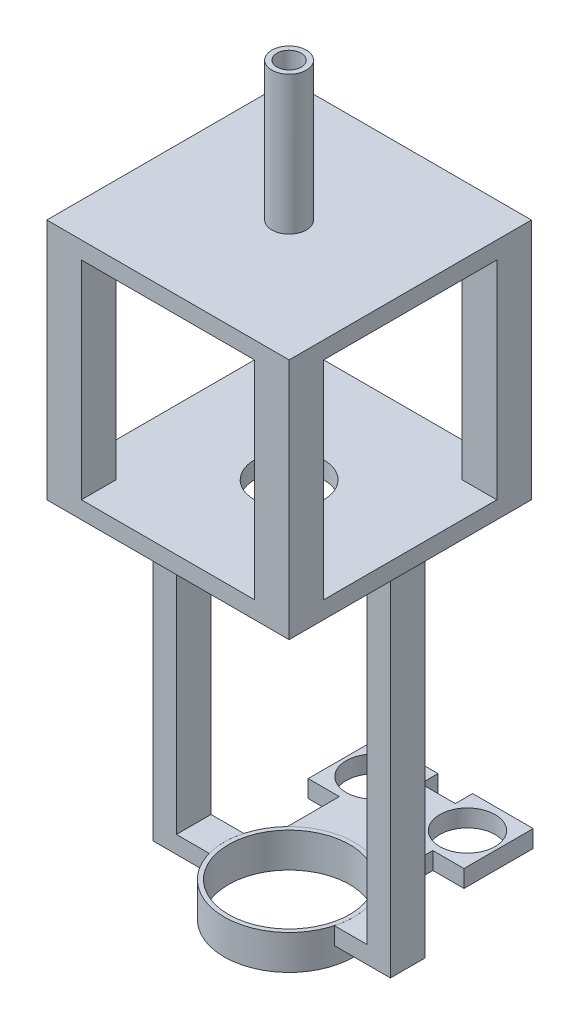
SolidWorks part; units mm, degrees
ref_plane "Front Plane" through (0, 0, 0) normal (0, 0, 1) x (1, 0, 0)
ref_plane "Top Plane" through (0, 0, 0) normal (0, 1, 0) x (1, 0, 0)
ref_plane "Right Plane" through (0, 0, 0) normal (1, 0, 0) x (0, 0, -1)
sketch "Sketch2" plane through (0, 0, 0) normal (0, 1, 0) x (1, 0, 0)
  line L0 (0, 17.5) -> (0, -17.5) construction
  line L1 (-17.5, 0) -> (17.5, 0) construction
  line L2 (-17.5, 0) -> (-17.5, 5) construction
  line L3 (-16.7705, 5) -> (-34.2705, 5)
  line L4 (-34.2705, 5) -> (-34.2705, -5)
  line L5 (-16.7705, -5) -> (-34.2705, -5)
  line L6 (16.7705, -5) -> (34.2705, -5)
  line L7 (34.2705, 5) -> (34.2705, -5)
  line L8 (16.7705, 5) -> (34.2705, 5)
  line L9 (0, 28.012) -> (22.5, 28.012)
  line L10 (22.5, 28.012) -> (22.5, 48.012)
  line L11 (22.5, 48.012) -> (5, 48.012)
  line L12 (-22.5, 48.012) -> (-22.5, 28.012)
  line L13 (-22.5, 28.012) -> (0, 28.012)
  line L14 (22.5, 38.012) -> (21.5, 38.012) construction
  line L20 (-5, 48.012) -> (-22.5, 48.012)
  line L21 (0, 43.012) -> (0, 28.012) construction
  line L22 (-5, 48.012) -> (-5, 43.012)
  line L23 (-5, 43.012) -> (5, 43.012)
  line L24 (5, 43.012) -> (5, 48.012)
  line L25 (13.5, 46.012) -> (13.5, 48.012) construction
  line L26 (13.5, 30.012) -> (13.5, 28.012) construction
  line L27 (-13.5, 38.012) -> (13.5, 38.012) construction
  line L28 (-13.5, 13.012) -> (-13.5, 28.012)
  line L29 (13.5, 28.012) -> (13.5, 13.012)
  line L30 (-18.75, 0) -> (-27.55, 0) construction
  line L31 (-27.55, 5) -> (-27.55, -5)
  line L32 (27.55, 5) -> (27.55, -5)
  circle A0 centre (0, 0) radius 17.5
  circle A1 centre (0, 0) radius 18.75
  circle A2 centre (13.5, 38.012) radius 8
  circle A3 centre (-13.5, 38.012) radius 8
  point P13 (-34.2705, 0)
  dimension "D1" = 35
  dimension "D2" = 17.5
  dimension "D4" = 37.5
  dimension "D8" = 1
  dimension "D9" = 16
  dimension "D3" = 5
  dimension "D5" = 5
  dimension "D6" = 20
  dimension "D7" = 45
  dimension "D10" = 17.5
  dimension "D11" = 8.8
  dimension "D12" = 27
  dimension "D13" = 15
extrude "Connector sleeve" add sketch "Sketch2" along normal blind 5 and the other way blind 5 contours L5 A1 L6 A0 | L8 A1 L3 A0 | L6 A1 L8 A0 | L3 A1 L5 A0 region at (-15.95, 0, -9.0999) region at (-17.8897, 0, 0) region at (-17.4208, 0, 5.3867) region at (17.8897, 0, 0)
ref_plane "Plane2" through (0, 30, 0) normal (0, 1, 0) x (1, 0, 0)
extrude "Sensor holder" add sketch "Sketch2<10>" along normal blind 5 separate body contours L24 L23 L22 L20 L12 L13 L9 L10 L11 A2 A3 | A1 L29 L9 L13 L28 | A1 L3 L31 L5 | L31 L3 L4 L5 | A1 L6 L32 L8 | L8 L32 L6 L7 region at (-30.9103, 0, 0) region at (-23.0354, 0, 0) region at (0, 0, -22.3672) region at (0, 0, -37.1747) region at (23.0354, 0, 0) region at (30.9103, 0, 0)
sketch "Sketch2<10>" plane through (0, 0, 0) normal (0, 1, 0) x (1, 0, 0) same geometry as "Sketch2"
extrude "Boss-Extrude1" add sketch "Sketch2<18>" along normal blind 100 contours L31 L3 L4 L5 | L8 L32 L6 L7 region at (-30.9103, 0, 0) region at (30.9103, 0, 0)
sketch "Sketch2<18>" plane through (0, 0, 0) normal (0, 1, 0) x (1, 0, 0) same geometry as "Sketch2"
sketch "Sketch4" plane through (0, 100, 0) normal (0, 1, 0) x (1, 0, 0)
  line L1 (-35, -35) -> (35, -35)
  line L2 (-35, -35) -> (-35, 35)
  line L3 (-35, 35) -> (35, 35)
  line L4 (35, -35) -> (35, 35)
  line L5 (-35, -35) -> (35, 35) construction
  line L6 (-35, 35) -> (35, -35) construction
  circle A0 centre (0, 0) radius 10
  point P0 (0, 0)
  dimension "D2" = 20
  dimension "D1" = 70
extrude "Boss-Extrude2" add sketch "Sketch4" along normal blind 5
sketch "Sketch6" plane through (0, 105, 0) normal (0, 1, 0) x (1, 0, 0)
  line L0 (-35, 35) -> (-25, 35)
  line L1 (35, 35) -> (-35, 35) construction
  line L2 (-25, 35) -> (-25, 25)
  line L3 (-25, 25) -> (-35, 25)
  line L4 (-35, 35) -> (-35, -35) construction
  line L5 (-35, 25) -> (-35, 35)
  line L6 (0, 35) -> (0, -35) construction
  line L7 (-35, -35) -> (35, -35) construction
  line L8 (-35, 0) -> (35, 0) construction
  line L9 (35, -35) -> (35, 35) construction
  line L10 (25, 25) -> (35, 25)
  line L11 (35, 25) -> (35, 35)
  line L12 (35, 35) -> (25, 35)
  line L13 (25, 35) -> (25, 25)
  line L14 (25, -25) -> (35, -25)
  line L15 (35, -25) -> (35, -35)
  line L16 (35, -35) -> (25, -35)
  line L17 (25, -35) -> (25, -25)
  line L18 (-25, -25) -> (-35, -25)
  line L19 (-25, -35) -> (-25, -25)
  line L20 (-35, -25) -> (-35, -35)
  line L21 (-35, -35) -> (-25, -35)
  dimension "D2" = 10
extrude "Boss-Extrude3" add sketch "Sketch6" along normal blind 60
sketch "Sketch7" plane through (0, 165, 0) normal (0, 1, 0) x (1, 0, 0)
  line L0 (-35, 35) -> (35, 35)
  line L1 (35, 35) -> (35, -35)
  line L2 (35, -35) -> (-35, -35)
  line L3 (-35, -25) -> (-35, -35) construction
  line L4 (-35, -35) -> (-35, 35)
extrude "Boss-Extrude4" add sketch "Sketch7" along normal blind 5 contours L1 L2 L4 L0
sketch "Sketch8" plane through (0, 170, 0) normal (0, 1, 0) x (1, 0, 0)
  circle A0 centre (0, 0) radius 5
  point P0 (0, 0)
  dimension "D1" = 10
extrude "Boss-Extrude5" add sketch "Sketch8" along normal blind 40
sketch "Sketch26" plane through (0, 210, 0) normal (0, 1, 0) x (1, 0, 0)
  circle A0 centre (0, 0) radius 3.5
  dimension "D1" = 7
extrude "Cut-Extrude1" cut sketch "Sketch26" against normal up to next (45 mm away)
